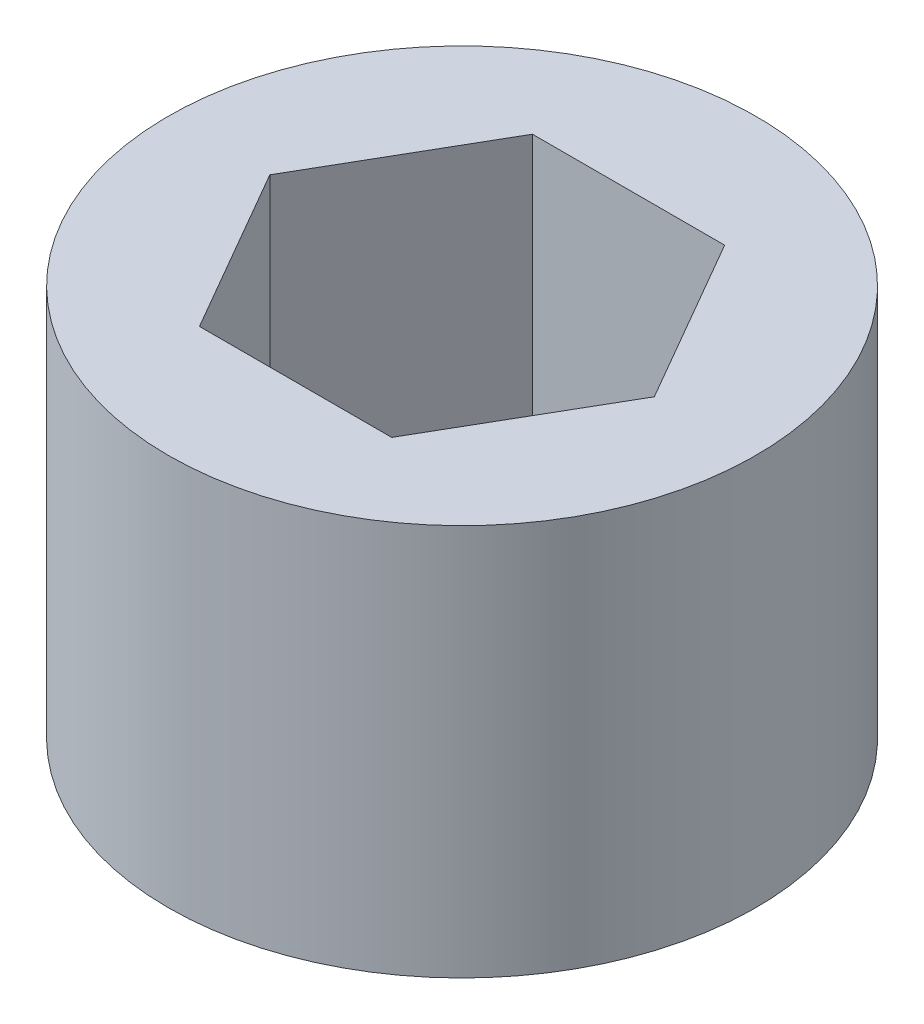
SolidWorks part; units mm, degrees
ref_plane "Front Plane" through (0, 0, 0) normal (0, 0, 1) x (1, 0, 0)
ref_plane "Top Plane" through (0, 0, 0) normal (0, 1, 0) x (1, 0, 0)
ref_plane "Right Plane" through (0, 0, 0) normal (1, 0, 0) x (0, 0, -1)
sketch "Sketch1" plane through (0, 0, 0) normal (0, 1, 0) x (1, 0, 0)
  line L1 (4.9075, 0) -> (2.4537, 4.25)
  line L2 (2.4537, 4.25) -> (-2.4537, 4.25)
  line L3 (-2.4537, 4.25) -> (-4.9075, 0)
  line L4 (-4.9075, 0) -> (-2.4537, -4.25)
  line L5 (-2.4537, -4.25) -> (2.4537, -4.25)
  line L6 (2.4537, -4.25) -> (4.9075, 0)
  circle A0 centre (0, 0) radius 4.25 construction
  circle A1 centre (0, 0) radius 7.5
  dimension "D2" = 15
  dimension "D1" = 8.5
extrude "Boss-Extrude1" add sketch "Sketch1" along normal blind 10
